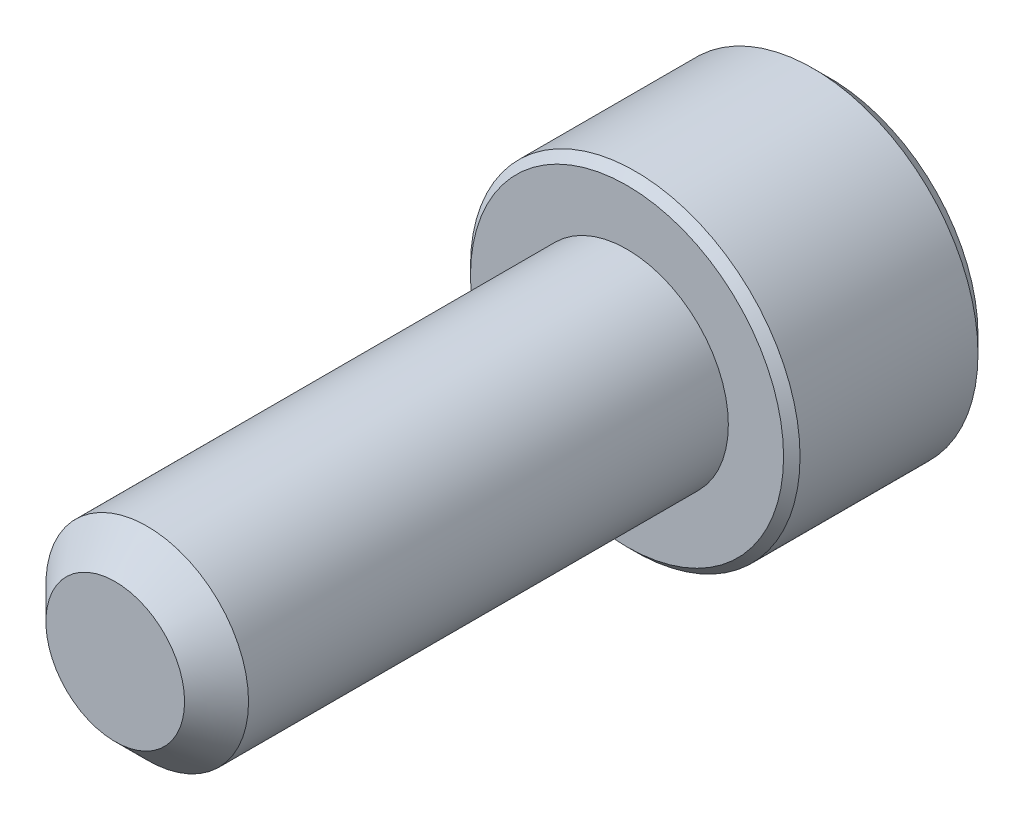
SolidWorks part; units mm, degrees
ref_plane "Front Plane" through (0, 0, 0) normal (0, 0, 1) x (1, 0, 0)
ref_plane "Top Plane" through (0, 0, 0) normal (0, 1, 0) x (1, 0, 0)
ref_plane "Right Plane" through (0, 0, 0) normal (1, 0, 0) x (0, 0, -1)
sketch "Sketch0" plane through (0, 0, 0) normal (1, 0, 0) x (0, 0, -1)
  line L0 (0, 0) -> (6.35, 0) construction
  point P2 (8.8646, 0)
  point P4 (0, 0)
  dimension "D1" = 6.35
  dimension "D2" = 2.5146
  dimension "Min Thread" = 0
sketch "Sketch1" plane through (0, 0, 0) normal (0, 0, 1) x (1, 0, 0)
  circle A0 centre (0, 0) radius 1.2573
  dimension "OD" = 2.5146
extrude "Extrude1" add sketch "Sketch1" against normal blind 6.35
sketch "Sketch2" plane through (0, 0, 0) normal (0, 0, 1) x (1, 0, 0)
  circle A0 centre (0, 0) radius 1.2573 construction
  circle A1 centre (0, 0) radius 1.2573
curve "Helix/Spiral1" [suppressed] parameters "pitch"=0.5292
chamfer "Chamfer3" distance 0.3969 angle 45 1 edges at (1.2573, 0, 0)
sketch "Sketch3" plane through (0, 0, 0) normal (1, 0, 0) x (0, 0, -1)
  line L0 (-0.463, 1.2573) -> (-0.2646, 0.9136)
  line L1 (-0.2646, 0.9136) -> (-0.1984, 0.9136)
  line L2 (-0.1984, 0.9136) -> (0, 1.2573)
  line L3 (-0.463, 1.2573) -> (0, 1.2573)
  line L4 (-0.2315, 1.2573) -> (-0.2315, 0.9136) construction
  line L5 (-0.3638, 1.0854) -> (-0.0992, 1.0854) construction
  line L6 (0, 1.2573) -> (0, -1.2573) construction
  dimension "D1" = 0.0661
  dimension "D2" = 0.2646
  dimension "D3" = 60
sweep "Cut-Sweep1" [suppressed] cut profiles "Sketch3" path "Helix/Spiral1"
sketch "Sketch5" [suppressed] plane through (0, 0, 0) normal (1, 0, 0) x (0, 0, -1)
  line L0 (9.525, -0.9237) -> (9.525, 0.8971) construction
  line L1 (9.525, 1.2573) -> (0, 1.2573)
  line L2 (9.525, 1.2573) -> (9.525, 0)
  line L3 (9.525, 0) -> (-0.4576, 0)
  line L4 (0, 0) -> (9.525, 0) construction
  line L5 (0, 1.2573) -> (-0.4576, 0)
  line L6 (0, 0) -> (12.065, 0) construction
  dimension "D1" = 70
  dimension "D3" = 2.54
revolve "partially thread" [suppressed] add sketch "Sketch5" angle 360 about L6
sketch "Sketch6" plane through (0, 0, -6.35) normal (0, 0, -1) x (-1, 0, 0)
  circle A0 centre (0, 0) radius 2.0447
  dimension "head dia" = 4.0894
extrude "Extrude2" add sketch "Sketch6" along normal blind 2.5146
sketch "Sketch7" plane through (0, 0, -8.8646) normal (0, 0, -1) x (-1, 0, 0)
  line L1 (0, 1.1457) -> (-0.9922, 0.5728)
  line L2 (-0.9922, 0.5728) -> (-0.9922, -0.5728)
  line L3 (-0.9922, -0.5728) -> (0, -1.1457)
  line L4 (0, -1.1457) -> (0.9922, -0.5728)
  line L5 (0.9922, -0.5728) -> (0.9922, 0.5728)
  line L6 (0.9922, 0.5728) -> (0, 1.1457)
  circle A0 centre (0, 0) radius 0.9922 construction
  dimension "hex dia" = 1.9844
extrude "Cut-Extrude1" cut sketch "Sketch7" against normal blind 1.4883
sketch "Sketch8" plane through (0, 0, -8.8646) normal (0, 0, -1) x (-1, 0, 0)
  circle A0 centre (0, 0) radius 1.1457
extrude "Cut-Extrude2" cut sketch "Sketch8" against normal through all draft 45
chamfer "Chamfer1" distance 0.2045 angle 45 1 edges at (-2.0447, 0, -8.8646)
chamfer "Chamfer2" distance 0.1022 angle 45 1 edges at (-2.0447, 0, -6.35)
sketch "Sketch9" plane through (0, 0, 0) normal (1, 0, 0) x (0, 0, -1)
  line L0 (0, 1.2573) -> (0, -1.2573) construction
  line L1 (1.8521, 1.2573) -> (1.8521, -1.2573) construction
  line L2 (8.8646, 2.0447) -> (8.8646, -2.0447) construction
  line L3 (6.35, 2.0447) -> (6.35, -2.0447) construction
  line L4 (6.35, 1.9425) -> (6.35, -1.9425) construction
  line L5 (8.8646, -1.8402) -> (8.8646, 1.8402) construction
  line L6 (6.35, -2.0447) -> (6.35, 2.0447) construction
  line L7 (0, 0.8604) -> (0, -0.8604) construction
  line L8 (-0.463, 1.2573) -> (0, 1.2573) construction
  line L9 (1.8521, 0) -> (0, 0) construction
  dimension "D1" = 1.8521
equation "\"D3@Helix/Spiral1\" = \"screw length@Extrude1\"+\"pitch@Helix/Spiral1\""
equation "\"D1@Sketch3\" = \"pitch@Helix/Spiral1\"*.125"
equation "\"D2@Sketch3\" = \"pitch@Helix/Spiral1\"*.5"
equation "\"D1@Cut-Extrude1\" = \"hex dia@Sketch7\"*.75"
equation "\"D1@Chamfer1\" = \"head dia@Sketch6\"*.05"
equation "\"D1@Sketch9\" = \"pitch@Helix/Spiral1\"*3.50"
equation "\"D1@Chamfer2\" = \"D1@Chamfer1\"/2"
equation "\"D1@Chamfer3\" = \"pitch@Helix/Spiral1\"*.750"
equation "\"D1@Sketch0\" = \"screw length@Extrude1\""
equation "\"D2@Sketch0\" = \"head depth@Extrude2\""
